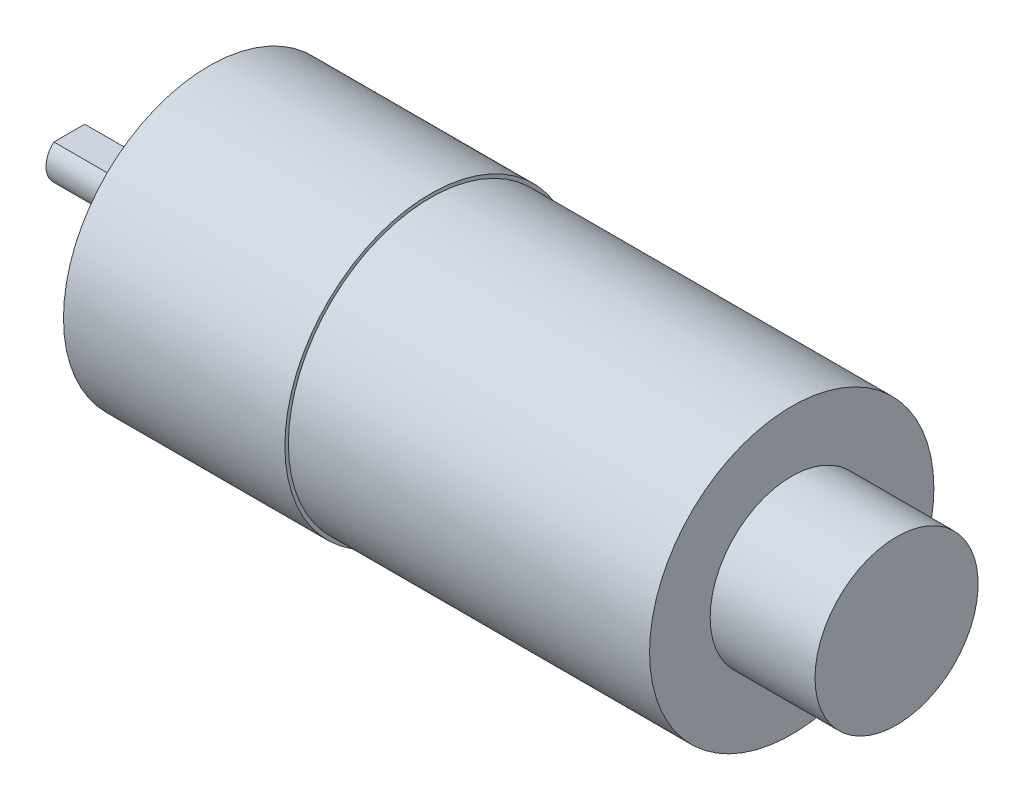
SolidWorks part; units mm, degrees
ref_plane "Front Plane" through (0, 0, 0) normal (0, 0, 1) x (1, 0, 0)
ref_plane "Top Plane" through (0, 0, 0) normal (0, 1, 0) x (1, 0, 0)
ref_plane "Right Plane" through (0, 0, 0) normal (1, 0, 0) x (0, 0, -1)
sketch "Sketch1" plane through (0, 0, 0) normal (0, 0, 1) x (1, 0, 0)
  line L0 (0, 0) -> (69.9216, 0) construction
  line L1 (0, 0) -> (0, 3.5)
  line L2 (0, 3.5) -> (2.5, 3.5)
  line L3 (2.5, 3.5) -> (2.5, 12.5)
  line L4 (2.5, 12.5) -> (21.5, 12.5)
  line L5 (21.5, 12.5) -> (21.5, 0)
  line L6 (0, 2) -> (-9.5, 2)
  line L7 (-9.5, 2) -> (-9.5, 0)
  line L8 (-9.5, 0) -> (0, 0)
  line L9 (21.5, 12.2) -> (52.5, 12.2)
  line L10 (52.5, 12.2) -> (52.5, 0)
  line L11 (52.5, 7) -> (61.5, 7)
  line L12 (61.5, 7) -> (61.5, 0)
  point P16 (69.9216, 0)
  point P18 (0, 0)
  dimension "D1" = 3.5
  dimension "D2" = 2
  dimension "D3" = 12.5
  dimension "D4" = 12.2
  dimension "D5" = 31
  dimension "D6" = 19
  dimension "D7" = 2.5
  dimension "D8" = 12
  dimension "D9" = 7
  dimension "D10" = 9
revolve "Revolve1" add sketch "Sketch1" angle 360 about L0 region at (11.618, 6.0901, 0) region at (-4.75, 1, 0) region at (37, 6.1, 0) region at (57, 3.5, 0)
sketch "Sketch2" plane through (-9.5, 0, 0) normal (-1, 0, 0) x (0, 0, 1)
  line L0 (0, -2) -> (0, 2) construction
  line L1 (2, 1.5) -> (-2, 1.5)
  line L2 (-2, 1.5) -> (-2, 2)
  line L3 (-2, 2) -> (2, 2)
  line L4 (2, 1.5) -> (2, 2)
  circle A0 centre (0, 0) radius 2 construction
  point P10 (0, 1.5)
  dimension "D1" = 4
  dimension "D2" = 3.5
extrude "Cut-Extrude1" cut sketch "Sketch2" against normal blind 8
